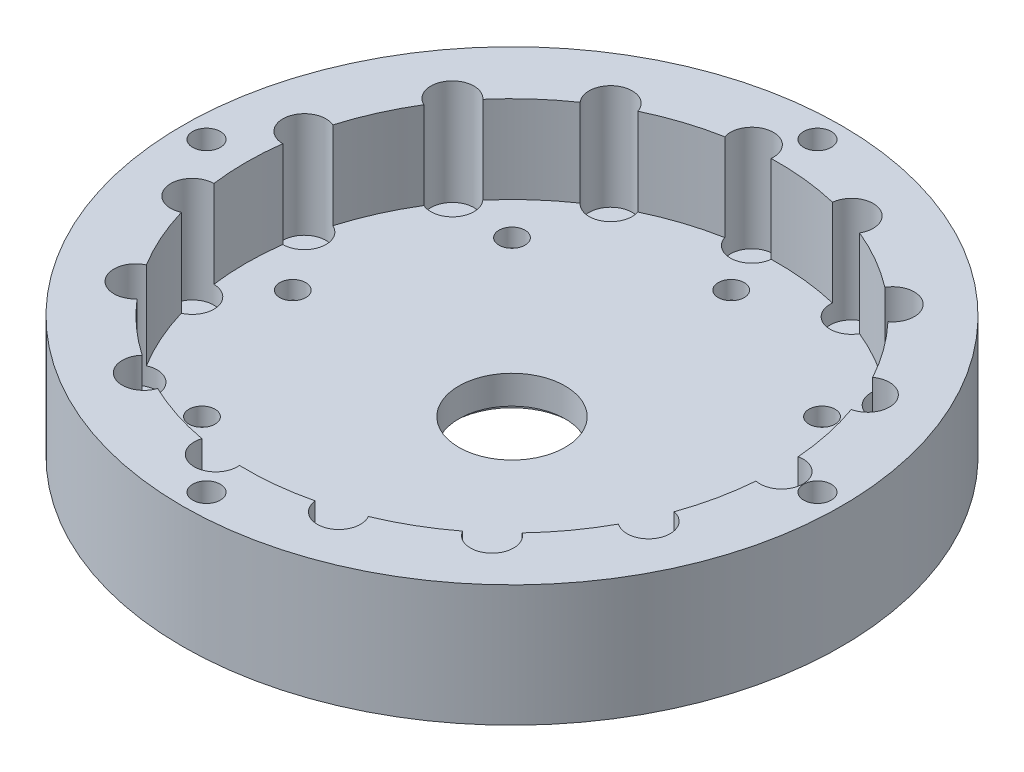
SolidWorks part; units mm, degrees
ref_plane "Front Plane" through (0, 0, 0) normal (0, 0, 1) x (1, 0, 0)
ref_plane "Top Plane" through (0, 0, 0) normal (0, 1, 0) x (1, 0, 0)
ref_plane "Right Plane" through (0, 0, 0) normal (1, 0, 0) x (0, 0, -1)
sketch "Sketch1" plane through (0, 0, 0) normal (0, 1, 0) x (1, 0, 0)
  line L0 (0, 0) -> (-42.5, 0) construction
  circle A0 centre (0, 0) radius 7.4
  circle A1 centre (0, 0) radius 45.85
  circle A2 centre (0, 0) radius 37.5 construction
  circle A3 centre (37.5, 0) radius 3
  circle A4 centre (34.258, 15.2526) radius 3
  circle A5 centre (25.0924, 27.8679) radius 3
  circle A6 centre (11.5881, 35.6646) radius 3
  circle A7 centre (-3.9198, 37.2946) radius 3
  circle A8 centre (-18.75, 32.476) radius 3
  circle A9 centre (-30.3381, 22.0419) radius 3
  circle A10 centre (-36.6805, 7.7967) radius 3
  circle A11 centre (-36.6805, -7.7967) radius 3
  circle A12 centre (-30.3381, -22.0419) radius 3
  circle A13 centre (-18.75, -32.476) radius 3
  circle A14 centre (-3.9198, -37.2946) radius 3
  circle A15 centre (11.5881, -35.6646) radius 3
  circle A16 centre (25.0924, -27.8679) radius 3
  circle A17 centre (34.258, -15.2526) radius 3
  circle A19 centre (0, 0) radius 30.5 construction
  circle A20 centre (30.5, 0) radius 1.8125
  circle A21 centre (21.5668, -21.5668) radius 1.8125
  circle A22 centre (0, -30.5) radius 1.8125
  circle A23 centre (-21.5668, -21.5668) radius 1.8125
  circle A24 centre (-30.5, 0) radius 1.8125
  circle A25 centre (-21.5668, 21.5668) radius 1.8125
  circle A26 centre (0, 30.5) radius 1.8125
  circle A27 centre (21.5668, 21.5668) radius 1.8125
  arc A28 (36.8833, 2.9359) -> (34.8888, 12.3197) centre (0, 0) ccw
  arc A29 (34.8888, -12.3197) -> (36.8833, -2.9359) centre (0, 0) ccw
  arc A30 (26.8616, -25.4451) -> (32.5004, -17.6839) centre (0, 0) ccw
  arc A31 (14.1898, -34.1709) -> (22.4979, -29.3742) centre (0, 0) ccw
  arc A32 (-0.9355, -36.9882) -> (8.6053, -35.9854) centre (0, 0) ccw
  arc A33 (-15.8991, -33.4099) -> (-6.7752, -36.3744) centre (0, 0) ccw
  arc A34 (-28.1135, -24.0547) -> (-20.9843, -30.4739) centre (0, 0) ccw
  arc A35 (-35.4669, -10.5403) -> (-31.5649, -19.3043) centre (0, 0) ccw
  arc A36 (-36.6878, 4.7967) -> (-36.6878, -4.7967) centre (0, 0) ccw
  arc A37 (-31.5649, 19.3043) -> (-35.4669, 10.5403) centre (0, 0) ccw
  arc A38 (-20.9843, 30.4739) -> (-28.1135, 24.0547) centre (0, 0) ccw
  arc A39 (-6.7752, 36.3744) -> (-15.8991, 33.4099) centre (0, 0) ccw
  arc A40 (8.6053, 35.9854) -> (-0.9355, 36.9882) centre (0, 0) ccw
  arc A41 (22.4979, 29.3742) -> (14.1898, 34.1709) centre (0, 0) ccw
  arc A42 (32.5004, 17.6839) -> (26.8616, 25.4451) centre (0, 0) ccw
  circle A43 centre (-42.5, 0) radius 1.5635
  circle A44 centre (0, 42.5) radius 1.5635
  circle A45 centre (42.5, 0) radius 1.5635
  circle A46 centre (0, 0) radius 8.25
  circle A47 centre (0, -42.5) radius 1.5635
  point P38 (0, 0)
  point P57 (0, 0)
  point P87 (0, 0)
  point P92 (0, 0)
  dimension "D2" = 14.8
  dimension "D3" = 75
  dimension "D4" = 91.7
  dimension "D5" = 6
  dimension "D8" = 3.625
  dimension "D9" = 61
  dimension "D6" = 37
  dimension "D12" = 3.127
  dimension "D14" = 16.5
  dimension "D11" = 42.5
  dimension "D1" = 15
  dimension "D7" = 8
  dimension "D10" = 15
  dimension "D13" = 4
extrude "Boss-Extrude1" add sketch "Sketch1" against normal blind 4.7625 contours A4 A42 A5 A41 A6 A40 A7 A39 A8 A38 A9 A37 A10 A36 A11 A35 A12 A34 A13 A33 A14 A32 A15 A31 A16 A30 A17 A29 A3 A28 A0 A20 A21 A22 A23 A24 A25 A26 A27 | A3 | A17 | A4 | A5 | A6 | A7 | A8 | A9 | A10 | A11 | A12 | A13 | A14 | A15 | A16 | A1 A42 A4 A28 A3 A29 A17 A30 A16 A31 A15 A32 A14 A33 A13 A34 A12 A35 A11 A36 A10 A37 A9 A38 A8 A39 A7 A40 A6 A41 A5 | A22 | A23 | A24 | A25 | A26 | A27 | A20 | A21 | A46 A0 region at (-44.5532, 0, 0) region at (37.5, 0, 0) region at (33.4543, 0, 0) region at (34.258, 0, -15.2526) region at (34.258, 0, 15.2526) region at (25.0924, 0, -27.8679) region at (25.0924, 0, 27.8679) region at (11.5881, 0, -35.6646) region at (11.5881, 0, 35.6646) region at (-3.9198, 0, -37.2946) region at (-3.9198, 0, 37.2946) region at (-18.75, 0, -32.476) region at (-18.75, 0, 32.476) region at (-30.3381, 0, -22.0419) region at (-30.3381, 0, 22.0419) region at (-36.6805, 0, -7.7967) region at (-36.6805, 0, 7.7967) region at (30.5, 0, 0) region at (21.5668, 0, 21.5668) region at (0, 0, 30.5) region at (-21.5668, 0, 21.5668) region at (-30.5, 0, 0) region at (-21.5668, 0, -21.5668) region at (0, 0, -30.5) region at (21.5668, 0, -21.5668) region at (-8.0167, 0, 0)
extrude "Cut-Extrude1" cut sketch "Sketch1<6>" against normal blind 2.5 contours A24 | A25 | A26 | A27 | A20 | A21 | A22 | A23 | A10 | A11 | A9 | A12 | A13 | A14 | A15 | A16 | A17 | A3 | A4 | A5 | A6 | A7 | A8 region at (37.5, 0, 0) region at (34.258, 0, -15.2526) region at (34.258, 0, 15.2526) region at (25.0924, 0, -27.8679) region at (25.0924, 0, 27.8679) region at (11.5881, 0, -35.6646) region at (11.5881, 0, 35.6646) region at (-3.9198, 0, -37.2946) region at (-3.9198, 0, 37.2946) region at (-18.75, 0, -32.476) region at (-18.75, 0, 32.476) region at (-30.3381, 0, -22.0419) region at (-30.3381, 0, 22.0419) region at (-36.6805, 0, -7.7967) region at (-36.6805, 0, 7.7967) region at (30.5, 0, 0) region at (21.5668, 0, 21.5668) region at (0, 0, 30.5) region at (-21.5668, 0, 21.5668) region at (-30.5, 0, 0) region at (-21.5668, 0, -21.5668) region at (0, 0, -30.5) region at (21.5668, 0, -21.5668)
sketch "Sketch1<6>" plane through (0, 0, 0) normal (0, 1, 0) x (1, 0, 0) same geometry as "Sketch1"
extrude "Boss-Extrude2" add sketch "Sketch1<7>" along normal blind 12.15 contours A1 A42 A4 A28 A3 A29 A17 A30 A16 A31 A15 A32 A14 A33 A13 A34 A12 A35 A11 A36 A10 A37 A9 A38 A8 A39 A7 A40 A6 A41 A5 region at (-44.5532, 0, 0)
sketch "Sketch1<7>" plane through (0, 0, 0) normal (0, 1, 0) x (1, 0, 0) same geometry as "Sketch1"
sketch "Sketch2" plane through (0, 12.15, 0) normal (0, 1, 0) x (1, 0, 0)
  circle A0 centre (-42.5, 0) radius 1.925
  circle A3 centre (0, 42.5) radius 1.925
  circle A4 centre (42.5, 0) radius 1.925
  circle A5 centre (0, -42.5) radius 1.925
  point P10 (0, 0)
  point P14 (0, 0)
  dimension "D2" = 3.85
  dimension "D1" = 4
extrude "Cut-Extrude2" cut sketch "Sketch2" against normal blind 4
extrude "Cut-Extrude3" cut sketch "Sketch1<8>" along normal blind 0.8 from offset 4.7625 contours A46 A0 region at (-8.0167, 0, 0) offset against normal yes
sketch "Sketch1<8>" plane through (0, 0, 0) normal (0, 1, 0) x (1, 0, 0) same geometry as "Sketch1"
equation "\"D2@Sketch1\"=\"smallBearOD\"+\"smallBearOTight\""
equation "\"D3@Sketch1\"=\"pinCircleDiam\""
equation "\"D5@Sketch1\"=\"pinDiam\""
equation "\"D8@Sketch1\"=\"ballBearDiam\"+0.125mm"
equation "\"D1@Cut-Extrude1\"=\"ballBearDiam\"-1mm"
equation "\"D1@Boss-Extrude2\"=\"ballBearDiam\"*0.75mm+2*\"sheetThickness\""
equation "\"largeBearOD\"= 21mm"
equation "\"largeBearID\" = 15mm"
equation "\"largeBearOTight\"= 0.34375mm'calibrate - hold onto gears"
equation "\"largeBearITight\"= 0mm'calibrate - hold onto eccentric nut"
equation "\"largeBearFlangeDiam\" = 22.5mm"
equation "\"largeBearFlangeWidth\" = 0.8mm"
equation "\"smallBearOD\"= 14.8mm"
equation "\"smallBearOTight\"= 0mm'calibrate - hold onto bottom of gearbox"
equation "\"smallBearOLoose\"= 0mm'calibrate - able to take off topHat"
equation "\"smallBearID\" = 10mm"
equation "\"smallBearITight\" = 0mm'hold onto "
equation "\"pinCircleDiam\"= 75mm"
equation "\"pinDiam\"= 6mm"
equation "\"sheetThickness\"= 0.1875in"
equation "\"ballBearDiam\"= 3.5mm"
equation "\"thrustBearingThickness\"= 5mm'measure this irl and change"
equation "\"thrustBearingID\"= 0mm'measure this irl and change"
equation "\"thrustBearingOD\"= 0mm'measure this irl and change"
equation "\"eccentricity\" = 1mm"
equation "\"D6@Sketch1\"=(\"pinCircleDiam\"-1)/2"
equation "\"D1@Boss-Extrude1\"=\"sheetThickness\""
equation "\"D19@Cut-Extrude3\"=\"sheetThickness\""
